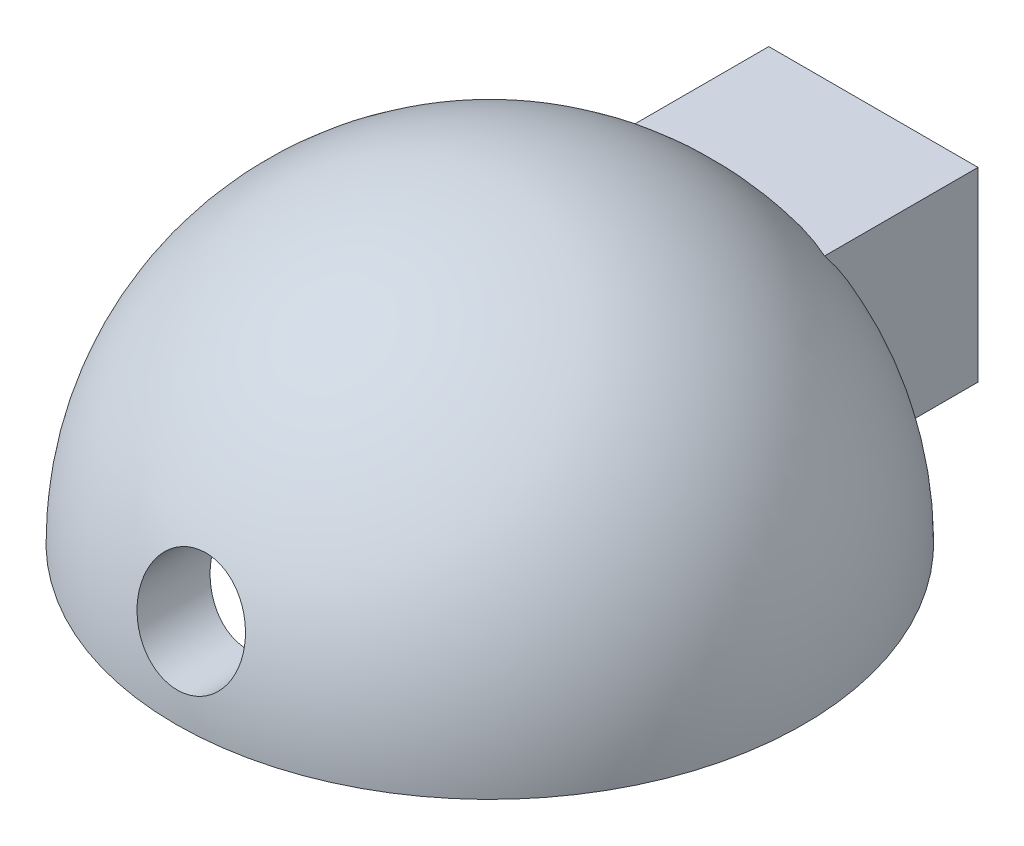
SolidWorks part; units mm, degrees
ref_plane "Front Plane" through (0, 0, 0) normal (0, 0, 1) x (1, 0, 0)
ref_plane "Top Plane" through (0, 0, 0) normal (0, 1, 0) x (1, 0, 0)
ref_plane "Right Plane" through (0, 0, 0) normal (1, 0, 0) x (0, 0, -1)
ref_plane "Plane1" through (-3.25, 0, 0) normal (-1, 0, 0) x (0, 0, 1)
sketch "Sketch2" plane through (-3.25, 0, 0) normal (-1, 0, 0) x (0, 0, 1)
  line L5 (11.872, 18.9513) -> (11.872, 21.9513)
  line L6 (1.372, 8.4513) -> (-1.628, 8.4513)
  line L7 (11.872, 21.9513) -> (11.872, 8.4513) construction
  line L8 (-1.628, 2.7013) -> (-1.628, 7.2013) construction
  line L9 (-1.628, 2.7013) -> (-1.628, 7.2013) construction
  arc A0 (11.872, 21.9513) -> (-1.628, 8.4513) centre (11.872, 8.4513) ccw
  arc A3 (11.872, 18.9513) -> (1.372, 8.4513) centre (11.872, 8.4513) ccw
  arc A4 (1.372, 8.4513) -> (1.4467, 7.2012) centre (11.872, 8.4513) ccw construction
  arc A5 (1.372, 8.4513) -> (1.4467, 7.2012) centre (11.872, 8.4513) ccw construction
  point P4 (0, 0)
  point P5 (0, 0)
  point P6 (0, 0)
  point P11 (0.8835, 8.4513)
  point P15 (0, 0)
  point P16 (41.2943, 8.4513)
revolve "Revolve1" add sketch "Sketch2" angle 360 about L7
sketch "Sketch3" plane through (0, 0, -4.628) normal (0, 0, 1) x (1, 0, 0)
  line L0 (-7.75, 8.4513) -> (1.25, 8.4513) construction
  line L1 (-7.75, 8.4513) -> (1.25, 8.4513)
  line L2 (-3.25, 6.2013) -> (-3.25, 8.4513) construction
  line L3 (-4.5, 11.9513) -> (-7.75, 11.9513) construction
  line L4 (-3.25, 13.2013) -> (-3.25, 16.4513) construction
  line L5 (-7.75, 8.4513) -> (1.25, 8.4513)
  line L6 (-7.75, 8.4513) -> (-7.75, 16.4513)
  line L7 (-7.75, 16.4513) -> (1.25, 16.4513)
  line L8 (1.25, 8.4513) -> (1.25, 16.4513)
  line L9 (-3.25, 10.7013) -> (-3.25, 8.4513) construction
  circle A2 centre (-3.25, 11.9513) radius 1.25
  circle A5 centre (-3.25, 4.9513) radius 1.25 construction
  circle A6 centre (-3.25, 4.9513) radius 1.25 construction
  circle M11 centre (-3.25, 11.9513) radius 1.25
extrude "Boss-Extrude1" add sketch "Sketch3" along normal up to surface (7.0132 mm away) contours L1 L8 L7 L6 M11 region at (-7.6296, 12.4513, -4.628) up to face at (-13.75, 8.4513, 11.872)
ref_plane "5mmHeadPlane" through (0, 0, -1.628) normal (0, 0, 1) x (1, 0, 0)
sketch "Sketch4" plane through (0, 0, -1.628) normal (0, 0, -1) x (-1, 0, 0)
  circle A4 centre (3.25, 11.9513) radius 2.25
  circle A5 centre (3.25, 11.9513) radius 2.25
  dimension "D1" = 1
extrude "Cut-Extrude1" cut sketch "Sketch4" against normal through all
